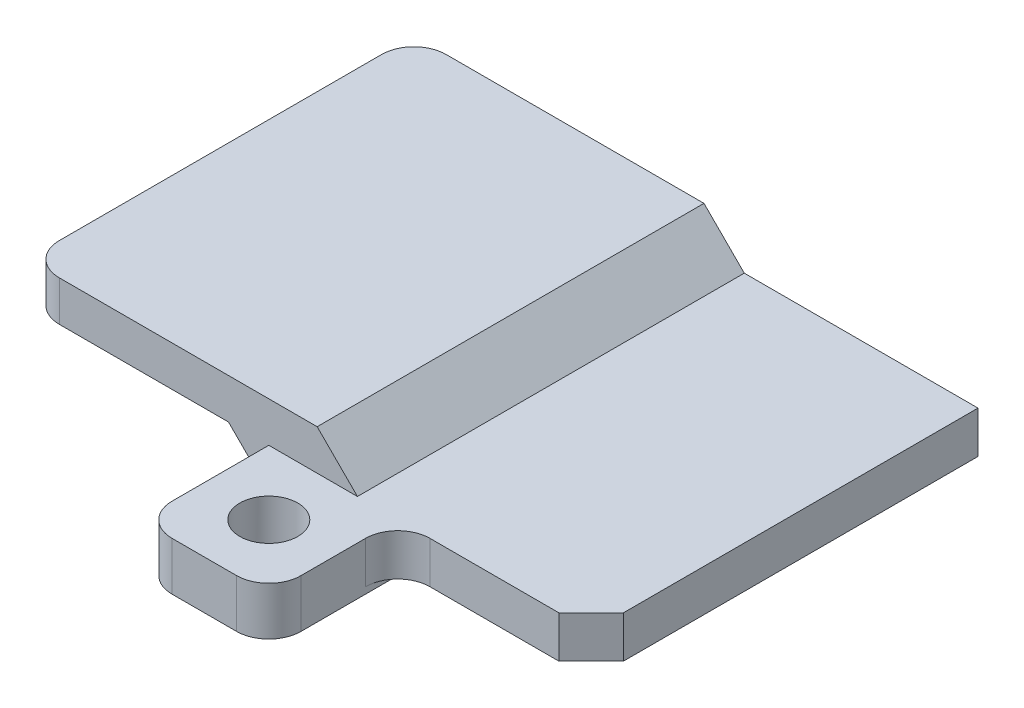
SolidWorks part; units mm, degrees
ref_plane "Płaszczyzna przednia" through (0, 0, 0) normal (0, 0, 1) x (1, 0, 0)
ref_plane "Płaszczyzna górna" through (0, 0, 0) normal (0, 1, 0) x (1, 0, 0)
ref_plane "Płaszczyzna prawa" through (0, 0, 0) normal (1, 0, 0) x (0, 0, -1)
sketch "Sketch1" plane through (0, 0, 0) normal (0, 1, 0) x (1, 0, 0)
  line L1 (0, 0) -> (20, 0)
  line L2 (0, 0) -> (0, 24)
  line L3 (0, 24) -> (20, 24)
  line L4 (20, 0) -> (20, 24)
  dimension "D1" = 24
  dimension "D2" = 20
extrude "Boss-Extrude1" add sketch "Sketch1" along normal blind 3
sketch "Sketch2" plane through (0, 3, 0) normal (0, 1, 0) x (1, 0, 0)
  line L0 (0, 24) -> (0, 0) construction
  line L1 (0, -8) -> (8, -8)
  line L2 (0, -8) -> (0, 0)
  line L3 (0, 0) -> (8, 0)
  line L4 (8, -8) -> (8, 0)
  line L5 (0, -8) -> (8, 0) construction
  line L6 (0, 0) -> (8, -8) construction
  line L7 (0, 0) -> (20, 0) construction
  circle A0 centre (4, -4) radius 1.8
  point P0 (4, -4)
  dimension "D2" = 3.6
  dimension "D1" = 8
extrude "Boss-Extrude2" add sketch "Sketch2" against normal up to surface (3 mm away) up to face at (10, 0, -12)
fillet "Fillet1" radius 2 3 edges at (8, 1.5, 0) (8, 1.5, 8) (0, 1.5, 8)
chamfer "Chamfer1" distance 2 angle 45 1 edges at (20, 1.5, 0)
sketch "Sketch3" plane through (0, 3, 0) normal (0, 1, 0) x (1, 0, 0)
  line L0 (20, 24) -> (0, 24) construction
  line L1 (3, 24) -> (-15, 24)
  line L2 (3, 24) -> (3, 0)
  line L3 (3, 0) -> (-15, 0)
  line L4 (-15, 24) -> (-15, 0)
  line L5 (10, 0) -> (18, 0) construction
  line L6 (0, 24) -> (0, -6) construction
  dimension "D1" = 18
  dimension "D2" = 3
extrude "Boss-Extrude3" add sketch "Sketch3" along normal blind 2.5
chamfer "Chamfer2" distance 2.5 angle 45 2 edges at (0, 3, -12) (3, 3, -12)
fillet "Fillet2" radius 2 2 edges at (-15, 4.25, -24) (-15, 4.25, 0)
sketch "Sketch4" plane through (0, 0, 0) normal (0, -1, 0) x (1, 0, 0)
  line L0 (8, 2) -> (8, 0)
  line L1 (0, 0) -> (8, 0)
  line L2 (0, 0) -> (0, -24)
  line L3 (0, -24) -> (20, -24)
  line L4 (20, 0) -> (20, -24)
  line L5 (8, 2) -> (20, 2)
  line L6 (20, 2) -> (20, 0)
  line M1 (20, -24) -> (20, -2)
  line M2 (20, -2) -> (18, 0)
  line M3 (18, 0) -> (10, 0)
  line M9 (0, 6) -> (0, -24)
  line M10 (0, -24) -> (20, -24)
extrude "Cut-Extrude3" cut sketch "Sketch4" against normal blind 0.4 contours L1 M9 M10 M1 M2 M3 region at (10.1905, 0, -11.381)
